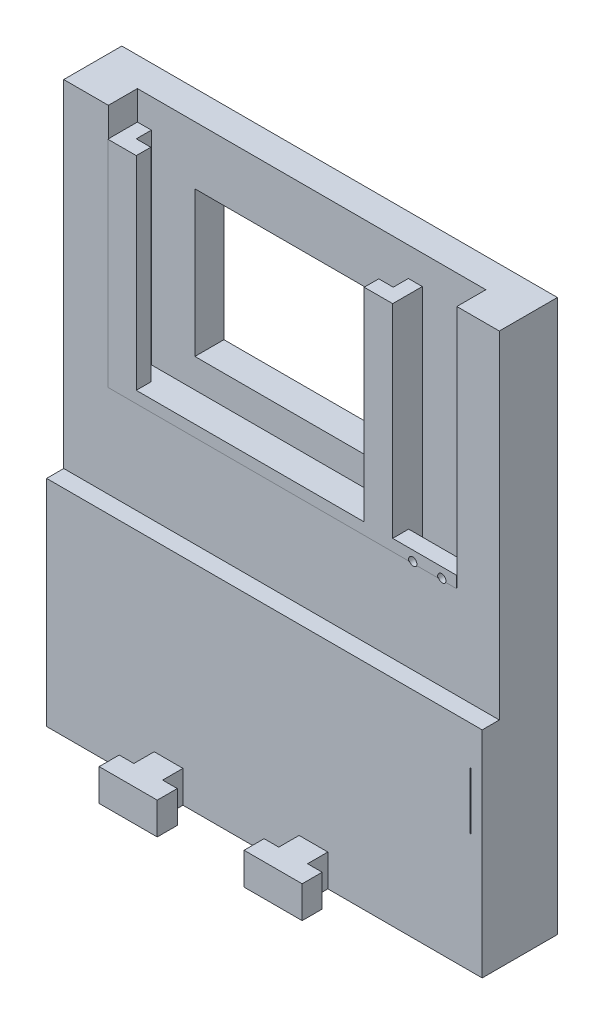
SolidWorks part; units mm, degrees
ref_plane "Front Plane" through (0, 0, 0) normal (0, 0, 1) x (1, 0, 0)
ref_plane "Top Plane" through (0, 0, 0) normal (0, 1, 0) x (1, 0, 0)
ref_plane "Right Plane" through (0, 0, 0) normal (1, 0, 0) x (0, 0, -1)
sketch "Sketch1" plane through (0, 0, 0) normal (0, 0, 1) x (1, 0, 0)
  line L1 (-60, -40) -> (60, -40)
  line L2 (-60, -40) -> (-60, 40)
  line L3 (-60, 40) -> (60, 40)
  line L4 (60, -40) -> (60, 40)
  line L5 (-60, -40) -> (60, 40) construction
  line L6 (-60, 40) -> (60, -40) construction
  point P0 (0, 0)
  dimension "D1" = 0
  dimension "D2" = 120
  dimension "80" = 80
extrude "Boss-Extrude1" add sketch "Sketch1" along normal blind 10
sketch "Sketch2" plane through (0, -40, 0) normal (0, -1, 0) x (1, 0, 0)
  line L0 (-60, 10) -> (60, 10) construction
  line L1 (-60, 10) -> (-55.2, 10)
  line L2 (-60, 10) -> (-60, 15.2)
  line L3 (-60, 15.2) -> (-55.2, 15.2)
  line L4 (-55.2, 10) -> (-55.2, 15.2)
  line L5 (-60, 20.2) -> (-50.2, 20.2)
  line L6 (-60, 20.2) -> (-60, 15.2)
  line L7 (-60, 15.2) -> (-50.2, 15.2)
  line L8 (-50.2, 20.2) -> (-50.2, 15.2)
  line L9 (38.1, 10) -> (33.3, 10)
  line L10 (38.1, 10) -> (38.1, 15.2)
  line L11 (38.1, 15.2) -> (33.3, 15.2)
  line L12 (33.3, 10) -> (33.3, 15.2)
  line L13 (28.3, 20.2) -> (38.1, 20.2)
  line L14 (28.3, 20.2) -> (28.3, 15.2)
  line L15 (28.3, 15.2) -> (38.1, 15.2)
  line L16 (38.1, 20.2) -> (38.1, 15.2)
  line L17 (-60, 10) -> (-60, 0) construction
  dimension "D1" = 0
  dimension "D2" = 0
  dimension "D3" = 0
  dimension "D4" = 5.2
  dimension "D5" = 9.8
  dimension "D6" = 5
  dimension "D7" = 4.8
  dimension "D8" = 9.8
  dimension "D9" = 5
  dimension "D10" = 0
  dimension "D11" = 0
  dimension "D12" = 0
  dimension "D13" = 5.2
  dimension "D14" = 4.8
  dimension "D15" = 88.5
  dimension "D16" = 0
extrude "Boss-Extrude2" add sketch "Sketch2" against normal blind 70 contours L8 L5 L6 L3 L7 | L16 L13 L14 L15 L11 | L4 L3 L2 L1 | L10 L11 L12 L9 region at (-55.1, -40, 17.7) region at (33.2, -40, 17.7)
sketch "Sketch3" plane through (0, 0, 10) normal (0, 0, 1) x (1, 0, 0)
  line L0 (-55.2, -40) -> (33.3, -40) construction
  line L1 (18.3, -30) -> (-40.2, -30)
  line L2 (18.3, -30) -> (18.3, 20)
  line L3 (18.3, 20) -> (-40.2, 20)
  line L4 (-40.2, -30) -> (-40.2, 20)
  line L5 (28.3, 30) -> (28.3, -40) construction
  line L6 (-50.2, 30) -> (-50.2, -40) construction
  line L7 (38.1, 30) -> (33.3, 30) construction
  dimension "D1" = 10
  dimension "D2" = 10
  dimension "D3" = 10
  dimension "D4" = 10
extrude "Cut-Extrude1" cut sketch "Sketch3" against normal blind 10
sketch "Sketch5" plane through (0, -40, 0) normal (0, -1, 0) x (-1, 0, 0)
  line L0 (60, -20.2) -> (50.2, -20.2) construction
  line L1 (60, -20.2) -> (-60, -20.2)
  line L2 (60, -20.2) -> (60, 0)
  line L3 (60, 0) -> (-60, 0)
  line L4 (-60, -20.2) -> (-60, 0)
  line L5 (60, -20.2) -> (60, 0) construction
  line L7 (60, 0) -> (-60, 0) construction
  line L8 (-60, -10) -> (-60, 0) construction
  dimension "D1" = 0
  dimension "D2" = 0
  dimension "D3" = 0
  dimension "D4" = 0
extrude "Boss-Extrude3" add sketch "Sketch5" along normal blind 4
sketch "Sketch6" plane through (0, 0, 0) normal (0, 0, -1) x (-1, 0, 0)
  line L0 (60, -44) -> (-60, -44) construction
  line L1 (60, -44) -> (-60, -44)
  line L2 (60, -44) -> (60, 40)
  line L3 (60, 40) -> (-60, 40)
  line L4 (-60, -44) -> (-60, 40)
  line L5 (75.3723, -150) -> (-74.6277, -150)
  line L6 (75.3723, -150) -> (75.3723, 40)
  line L7 (75.3723, 40) -> (-74.6277, 40)
  line L8 (-74.6277, -150) -> (-74.6277, 40)
  line L9 (60, 40) -> (60, -44) construction
  line L10 (-60, 40) -> (60, 40) construction
  line L11 (-60, -44) -> (-60, 40) construction
  line M5 (-60, 40) -> (-60, -44)
  line M6 (-60, -44) -> (60, -44)
  line M7 (60, -44) -> (60, 40)
  dimension "D1" = 0
  dimension "D2" = 0
  dimension "D3" = 0
  dimension "D4" = 0
  dimension "D5" = 150
  dimension "D6" = 190
  dimension "D7" = 0
extrude "Boss-Extrude5" add sketch "Sketch6" against normal blind 20 contours L8 L5 L6 L7 M7 M6 M5 region at (-0.576, -84.0033, 0)
sketch "Sketch7" plane through (0, 0, 20) normal (0, 0, 1) x (1, 0, 0)
  line L0 (74.6277, -150) -> (74.6277, 40) construction
  line L1 (74.6277, -76) -> (-75.3723, -76)
  line L2 (74.6277, -76) -> (74.6277, -150)
  line L3 (74.6277, -150) -> (-75.3723, -150)
  line L4 (-75.3723, -76) -> (-75.3723, -150)
  line L5 (70.7614, -89.3834) -> (70.4933, -89.3834)
  line L6 (70.7614, -89.3834) -> (70.7614, -108.9872)
  line L7 (70.7614, -108.9872) -> (70.4933, -108.9872)
  line L8 (70.4933, -89.3834) -> (70.4933, -108.9872)
  line L9 (-75.3723, -150) -> (74.6277, -150) construction
  line L10 (-75.3723, -150) -> (-75.3723, 40) construction
  line L11 (60, -44) -> (-60, -44) construction
  dimension "D1" = 0
  dimension "D2" = 0
  dimension "D3" = 0
  dimension "D4" = 32
extrude "Boss-Extrude6" add sketch "Sketch7" along normal blind 5.9
sketch "Sketch8" plane through (0, -150, 0) normal (0, -1, 0) x (1, 0, 0)
  line L0 (-75.3723, 25.9) -> (74.6277, 25.9) construction
  line L1 (-38.3223, 32.9) -> (-28.4223, 32.9)
  line L2 (-38.3223, 32.9) -> (-38.3223, 25.9)
  line L3 (-38.3223, 25.9) -> (-28.4223, 25.9)
  line L4 (-28.4223, 32.9) -> (-28.4223, 25.9)
  line L5 (11.5777, 32.9) -> (21.4777, 32.9)
  line L6 (11.5777, 32.9) -> (11.5777, 25.9)
  line L7 (11.5777, 25.9) -> (21.4777, 25.9)
  line L8 (21.4777, 32.9) -> (21.4777, 25.9)
  line L9 (-43.3723, 39.8) -> (-23.3723, 39.8)
  line L10 (-43.3723, 39.8) -> (-43.3723, 32.9)
  line L11 (-43.3723, 32.9) -> (-23.3723, 32.9)
  line L12 (-23.3723, 39.8) -> (-23.3723, 32.9)
  line L13 (6.5277, 39.8) -> (26.5277, 39.8)
  line L14 (6.5277, 39.8) -> (6.5277, 32.9)
  line L15 (6.5277, 32.9) -> (26.5277, 32.9)
  line L16 (26.5277, 39.8) -> (26.5277, 32.9)
  line L17 (-75.3723, 25.9) -> (-75.3723, 0) construction
  line M3 (74.6277, 25.9) -> (-75.3723, 25.9)
  dimension "D1" = 0
  dimension "D2" = 7
  dimension "D3" = 0
  dimension "D4" = 6.9
  dimension "D5" = 20
  dimension "D6" = 9.9
  dimension "D7" = 5.05
  dimension "D8" = 32
  dimension "D9" = 0
  dimension "D10" = 7
  dimension "D11" = 9.9
  dimension "D12" = 0
  dimension "D13" = 20
  dimension "D14" = 6.9
  dimension "D15" = 5.05
  dimension "D16" = 40
extrude "Boss-Extrude7" add sketch "Sketch8" against normal blind 11 contours L12 L9 L10 L11 L1 | L4 L1 L2 M3 | L16 L13 L14 L15 L5 | L8 L5 L6 M3 region at (-33.3723, -150, 36.35) region at (-33.3723, -150, 29.4) region at (16.5277, -150, 29.4) region at (16.5277, -150, 36.35)
sketch "Sketch21" plane through (0, -40, 0) normal (0, 1, 0) x (1, 0, 0)
  line L0 (60, -10) -> (60, -20) construction
  line L1 (60, -14.7) -> (38.1, -14.7)
  line L2 (60, -14.7) -> (60, -10)
  line L3 (60, -10) -> (38.1, -10)
  line L4 (38.1, -14.7) -> (38.1, -10)
  line L5 (38.1, -10) -> (60, -10) construction
  line L6 (38.1, -20.2) -> (38.1, -10) construction
  dimension "D1" = 0
  dimension "D2" = 0
  dimension "D3" = 4.7
  dimension "D4" = 0
extrude "Cut-Extrude7" cut sketch "Sketch21" against normal blind 5.5
sketch "Sketch22" plane through (0, 0, 20.2) normal (0, 0, 1) x (1, 0, 0)
  line L0 (60, -40) -> (38.1, -40) construction
  line L1 (60, -40) -> (60, -44) construction
  circle A0 centre (55, -43.5) radius 1.425
  circle A1 centre (45, -43.5) radius 1.425
  dimension "D1" = 2.85
  dimension "D2" = 2.85
  dimension "D4" = 3.5
  dimension "D3" = 3.5
  dimension "D5" = 5
  dimension "D6" = 10
extrude "Cut-Extrude8" cut sketch "Sketch22" against normal blind 5.5
